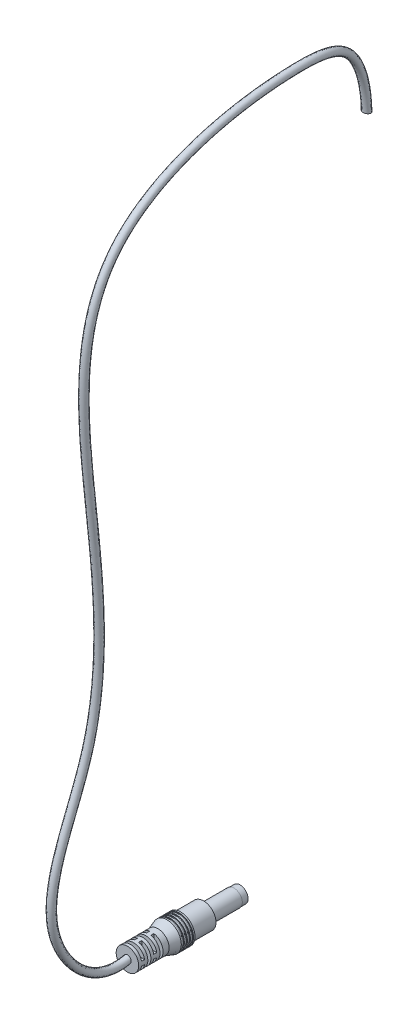
SolidWorks part; units mm, degrees
material "PA Type 6"
ref_plane "Piano frontale" through (0, 0, 0) normal (0, 0, 1) x (1, 0, 0)
ref_plane "Piano superiore" through (0, 0, 0) normal (0, 1, 0) x (1, 0, 0)
ref_plane "Piano destro" through (0, 0, 0) normal (1, 0, 0) x (0, 0, -1)
sketch "Sketch1" plane through (0, 0, 0) normal (0, 0, 1) x (1, 0, 0)
  circle A0 centre (0, 0) radius 2.75
  circle A1 centre (0, 0) radius 1.05
  dimension "D1" = 5.5
  dimension "D2" = 2.1
extrude "Boss-Extrude1" add sketch "Sketch1" along normal blind 10
sketch "Sketch2" plane through (0, 0, 0) normal (0, 0, -1) x (-1, 0, 0)
  circle A0 centre (0, 0) radius 2.65
  circle A1 centre (0, 0) radius 1.05
  dimension "D1" = 5.3
extrude "Boss-Extrude2" add sketch "Sketch2" along normal blind 2
chamfer "Chamfer1" distance 0.6 angle 45 1 edges at (-1.05, 0, -2)
sketch "Sketch3" plane through (0, 0, 10) normal (0, 0, 1) x (1, 0, 0)
  circle A0 centre (0, 0) radius 4.1
  dimension "D1" = 8.2
extrude "Boss-Extrude3" add sketch "Sketch3" along normal blind 7.5
sketch "Sketch5" plane through (0, 0, 0) normal (1, 0, 0) x (0, 0, -1)
  line L0 (-17.5, 0) -> (-17.5, 4.7)
  line L1 (-17.5, 4.1) -> (-17.5, -4.1) construction
  line L2 (-17.5, 4.7) -> (-18, 4.7)
  line L3 (-18, 4.7) -> (-18, 4.4)
  line L4 (-18, 4.4) -> (-18.5, 4.4)
  line L5 (-18.5, 4.4) -> (-18.5, 4.7)
  line L6 (-18.5, 4.7) -> (-19, 4.7)
  line L7 (-19, 4.7) -> (-19, 4.4)
  line L8 (-19, 4.4) -> (-19.5, 4.4)
  line L9 (-19.5, 4.4) -> (-19.5, 4.7)
  line L10 (-19.5, 4.7) -> (-20, 4.7)
  line L11 (-20, 4.7) -> (-20, 4.4)
  line L12 (-20, 4.4) -> (-20.5, 4.4)
  line L13 (-20.5, 4.4) -> (-20.5, 4.7)
  line L14 (-20.5, 4.7) -> (-21, 4.7)
  line L15 (-21, 4.7) -> (-21, 4.4)
  line L16 (-21, 4.4) -> (-21.5, 4.4)
  line L17 (-21.5, 4.4) -> (-21.5, 4.7)
  line L18 (-21.5, 4.7) -> (-22, 4.7)
  line L21 (-25, 3.7) -> (-22, 4.7)
  line L22 (-25, 3.7) -> (-25, 0)
  line L23 (-25, 0) -> (-17.5, 0)
  dimension "D1" = 4.7
  dimension "D2" = 0.5
  dimension "D3" = 0.3
  dimension "D4" = 0.5
  dimension "D5" = 0.5
  dimension "D6" = 0.5
  dimension "D7" = 0.5
  dimension "D8" = 0.5
  dimension "D9" = 0.5
  dimension "D10" = 0.5
  dimension "D11" = 0.5
revolve "Revolve1" add sketch "Sketch5" angle 360 about L23
sketch "Sketch6" plane through (0, 0, 25) normal (0, 0, 1) x (1, 0, 0)
  circle A0 centre (0, 0) radius 3.7
extrude "Boss-Extrude4" add sketch "Sketch6" along normal blind 10
sketch "Sketch7" plane through (0, 0, 0) normal (1, 0, 0) x (0, 0, -1)
  line L0 (-34, 3.7) -> (-34, 0.7)
  line L1 (-25, 3.7) -> (-35, 3.7) construction
  line L2 (-34, 0.7) -> (-33, 0.7)
  line L3 (-33, 0.7) -> (-33, 3.7)
  line L4 (-33, 3.7) -> (-34, 3.7)
  line L5 (-35, 3.7) -> (-35, -3.7) construction
  line L6 (-34, -3.7) -> (-34, -0.7)
  line L7 (-35, -3.7) -> (-25, -3.7) construction
  line L8 (-34, -0.7) -> (-33, -0.7)
  line L9 (-33, -0.7) -> (-33, -3.7)
  line L10 (-33, -3.7) -> (-34, -3.7)
  line L11 (-30, 3.7) -> (-30, 0.7)
  line L12 (-30, 0.7) -> (-29, 0.7)
  line L13 (-29, 0.7) -> (-29, 3.7)
  line L14 (-29, 3.7) -> (-30, 3.7)
  line L15 (-30, -3.7) -> (-30, -0.7)
  line L16 (-30, -0.7) -> (-29, -0.7)
  line L17 (-29, -0.7) -> (-29, -3.7)
  line L18 (-29, -3.7) -> (-30, -3.7)
  dimension "D1" = 3
  dimension "D2" = 1
  dimension "D3" = 1
  dimension "D4" = 3
  dimension "D5" = 1
  dimension "D6" = 3
extrude "Cut-Extrude1" cut sketch "Sketch7" against normal through all and the other way blind 10
sketch "Sketch8" plane through (0, 0, 0) normal (0, 1, 0) x (1, 0, 0)
  line L0 (-3.7, -32) -> (-0.7, -32)
  line L1 (-3.7, -25) -> (-3.7, -35) construction
  line L2 (-0.7, -32) -> (-0.7, -31)
  line L3 (-0.7, -31) -> (-3.7, -31)
  line L4 (-3.7, -31) -> (-3.7, -32)
  line L5 (-3.7, -35) -> (3.7, -35) construction
  line L6 (3.7, -32) -> (0.7, -32)
  line L7 (3.7, -35) -> (3.7, -25) construction
  line L8 (0.7, -32) -> (0.7, -31)
  line L9 (0.7, -31) -> (3.7, -31)
  line L10 (3.7, -31) -> (3.7, -32)
  line L11 (-3.7, -28) -> (-0.7, -28)
  line L12 (-0.7, -28) -> (-0.7, -27)
  line L13 (-0.7, -27) -> (-3.7, -27)
  line L14 (-3.7, -27) -> (-3.7, -28)
  line L15 (3.7, -28) -> (0.7, -28)
  line L16 (0.7, -28) -> (0.7, -27)
  line L17 (0.7, -27) -> (3.7, -27)
  line L18 (3.7, -27) -> (3.7, -28)
  dimension "D1" = 3
  dimension "D2" = 1
  dimension "D3" = 3
  dimension "D4" = 3
  dimension "D5" = 1
  dimension "D6" = 3
  dimension "D7" = 3
extrude "Cut-Extrude2" cut sketch "Sketch8" against normal through all and the other way blind 10
sketch "Sketch11" plane through (0, 0, 0) normal (1, 0, 0) x (0, 0, -1)
  line L1 (-35, 3.7) -> (-35, -3.7) construction
  spline S2 degree 3 poles (-35, 0) (-37.3491, -0.5589) (-48.1137, -0.1739) (-68.8333, 25.9155) (-23.2696, 92.5289) (-78.3146, 202.9478) (3.9055, 227.1141) (40.6025, 225.1617) (43.4734, 208.8105) (43.5786, 202.0079) knots 0 0 0 0 0.022579 0.097691 0.251206 0.689694 0.879221 0.933188 1 1 1 1
sketch "Sketch12" plane through (0, 0, 35) normal (0, 0, 1) x (1, 0, 0)
  circle A0 centre (0, 0) radius 1.25
sweep "Sweep1" add profiles "Sketch12" path "Sketch11"
